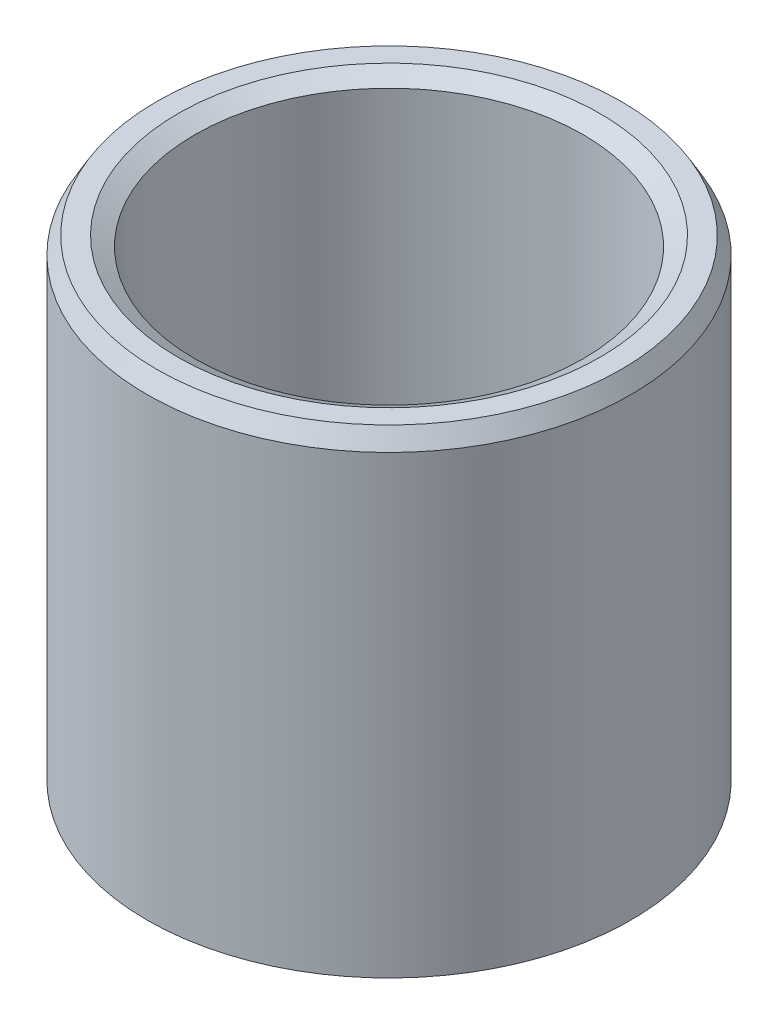
SolidWorks part; units mm, degrees
ref_plane "Front Plane" through (0, 0, 0) normal (0, 0, 1) x (1, 0, 0)
ref_plane "Top Plane" through (0, 0, 0) normal (0, 1, 0) x (1, 0, 0)
ref_plane "Right Plane" through (0, 0, 0) normal (1, 0, 0) x (0, 0, -1)
sketch "Sketch1" plane through (0, 0, 0) normal (0, 1, 0) x (1, 0, 0)
  circle A0 centre (0, 0) radius 52.5
  dimension "SLEEVE_OD" = 105
extrude "Boss-Extrude1" add sketch "Sketch1" along normal blind 104.5544
sketch "Sketch2" plane through (0, 0, 0) normal (0, 1, 0) x (1, 0, 0)
  circle A0 centre (0, 0) radius 42.131
  dimension "BORE_D" = 84.2619
extrude "Cut-Extrude1" cut sketch "Sketch2" along normal through all
chamfer "Chamfer1" distance 3.6728 angle 30 4 edges at (0, 104.5544, 42.131) (0, 0, 42.131) (0, 0, 52.5) (0, 104.5544, 52.5) first distance on face at (0, 104.5544, 42.131) first distance on face at (0, 0, 42.131) first distance on face at (0, 104.5544, 52.5)
